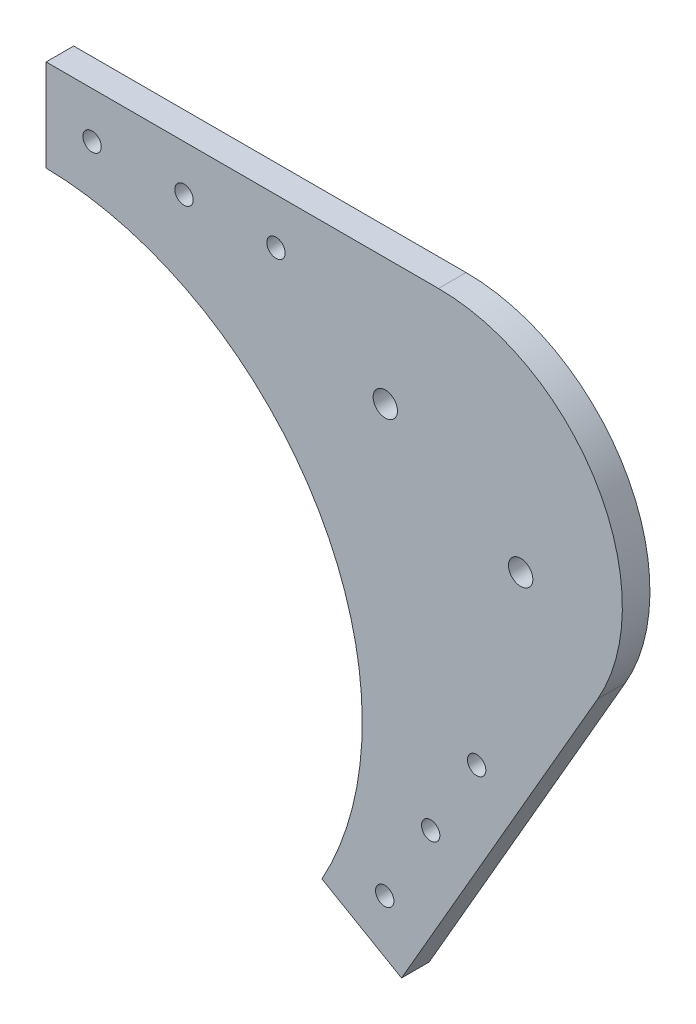
SolidWorks part; units mm, degrees
ref_plane "前视基准面" through (0, 0, 0) normal (0, 0, 1) x (1, 0, 0)
ref_plane "上视基准面" through (0, 0, 0) normal (0, 1, 0) x (1, 0, 0)
ref_plane "右视基准面" through (0, 0, 0) normal (1, 0, 0) x (0, 0, -1)
sketch "草图1" plane through (0, 0, 0) normal (0, 0, 1) x (1, 0, 0)
  line L0 (0, 0) -> (120, 0)
  line L1 (120, 0) -> (60, -103.923)
  line L2 (0, 0) -> (0, 20)
  line L3 (0, 20) -> (154.641, 20)
  line L4 (154.641, 20) -> (77.3205, -113.923)
  line L5 (77.3205, -113.923) -> (60, -103.923)
  dimension "D1" = 120
  dimension "D2" = 120
  dimension "D3" = 60
  dimension "D4" = 20
  dimension "D5" = 20
extrude "凸台-拉伸1" add sketch "草图1" along normal blind 6
fillet "圆角1" radius 70 1 edges at (120, 0, 3)
fillet "圆角2" radius 40 1 edges at (154.641, 20, 3)
sketch "草图2" plane through (0, 0, 6) normal (0, 0, 1) x (1, 0, 0)
  line L0 (77.3205, -113.923) -> (120, -40) construction
  line L1 (35.7207, 14.4322) -> (42314.3268, -24395.1325) construction
  circle A5 centre (103.2326, -24.5458) radius 2.65
  circle A6 centre (73.7877, -7.5458) radius 2.65
  point P6 (85.359, -20)
  dimension "D1" = 5.3
  dimension "D2" = 5.3
  dimension "D3" = 34
  dimension "D4" = 17
  dimension "D5" = 5
extrude "切除-拉伸1" cut sketch "草图2" against normal through all both and the other way through all
sketch "草图3" plane through (0, 0, 6) normal (0, 0, 1) x (1, 0, 0)
  line L0 (-4.8769, 10) -> (72.4812, 10) construction
  line L1 (85.359, 20) -> (0, 20) construction
  line L2 (66.3274, -112.9637) -> (93.3816, -66.1045) construction
  line L3 (77.3205, -113.923) -> (120, -40) construction
  line L4 (0, 20) -> (0, 0) construction
  line L5 (60, -103.923) -> (77.3205, -113.923) construction
  line L6 (73.6603, -100.2628) -> (83.6603, -82.9423) construction
  circle A0 centre (10, 10) radius 2
  circle A1 centre (30, 10) radius 2
  circle A2 centre (50, 10) radius 2
  circle A3 centre (73.6603, -100.2628) radius 2
  circle A4 centre (83.6603, -82.9423) radius 2
  circle A5 centre (93.6603, -65.6218) radius 2
  dimension "D2" = 4
  dimension "D3" = 4
  dimension "D5" = 10
  dimension "D6" = 20
  dimension "D7" = 4
  dimension "D8" = 20
  dimension "D9" = 4
  dimension "D10" = 10
  dimension "D1" = 10
  dimension "D4" = 10
  dimension "D12" = 20
  dimension "D11" = 3
extrude "切除-拉伸2" cut sketch "草图3" against normal blind 10
